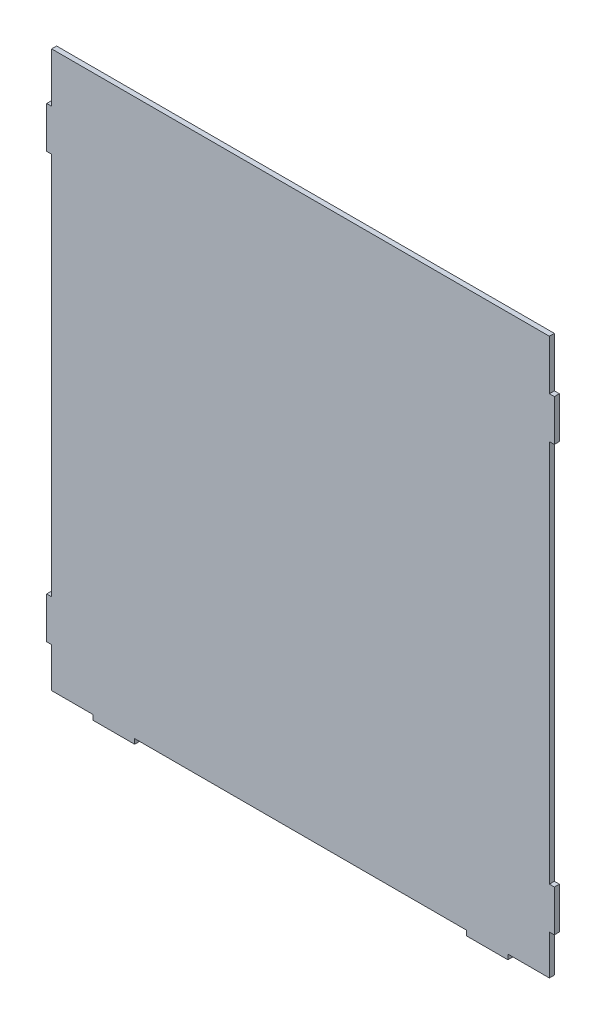
SolidWorks part; units mm, degrees
material "Maple"
ref_plane "Front Plane" through (0, 0, 0) normal (0, 0, 1) x (1, 0, 0)
ref_plane "Top Plane" through (0, 0, 0) normal (0, 1, 0) x (1, 0, 0)
ref_plane "Right Plane" through (0, 0, 0) normal (1, 0, 0) x (0, 0, -1)
sketch "Sketch1" plane through (0, 0, 0) normal (0, 0, 1) x (1, 0, 0)
  line L0 (6.0247, 322.5684) -> (6.0247, 175) construction
  line L1 (-293.9753, 322.5684) -> (306.0247, 322.5684)
  line L2 (-293.9753, 322.5684) -> (-293.9753, 262.5684)
  line L3 (-293.9753, -347.4316) -> (-243.9753, -347.4316)
  line L4 (306.0247, 322.5684) -> (306.0247, 262.5684)
  line L5 (-293.9753, -299.4316) -> (-293.9753, -347.4316)
  line L6 (-293.9753, 212.5684) -> (-293.9753, -249.4316)
  line L7 (306.0247, -299.4316) -> (306.0247, -347.4316)
  line L12 (306.0247, 212.5684) -> (306.0247, -249.4316)
  line L13 (6.0247, 322.5684) -> (6.0247, -377.5) construction
  line L14 (256.0247, -347.4316) -> (256.0247, -353.4316)
  line L21 (256.0247, -353.4316) -> (206.0247, -353.4316)
  line L22 (-193.9753, -347.4316) -> (206.0247, -347.4316)
  line L23 (312.0247, 212.5684) -> (306.0247, 212.5684)
  line L24 (6.0247, 175) -> (15.5145, 175) construction
  line L32 (-243.9753, -347.4316) -> (-243.9753, -353.4316)
  line L39 (-299.9753, 262.5684) -> (-293.9753, 262.5684)
  line L40 (-299.9753, 262.5684) -> (-299.9753, 212.5684)
  line L41 (-299.9753, 212.5684) -> (-293.9753, 212.5684)
  line L43 (-243.9753, -353.4316) -> (-193.9753, -353.4316)
  line L44 (-193.9753, -347.4316) -> (-193.9753, -353.4316)
  line L46 (312.0247, 262.5684) -> (306.0247, 262.5684)
  line L47 (312.0247, 262.5684) -> (312.0247, 212.5684)
  line L54 (-299.9753, -299.4316) -> (-293.9753, -299.4316)
  line L56 (206.0247, -347.4316) -> (206.0247, -353.4316)
  line L57 (256.0247, -347.4316) -> (306.0247, -347.4316)
  line L58 (306.0247, -249.4316) -> (312.0247, -249.4316)
  line L59 (312.0247, -249.4316) -> (312.0247, -299.4316)
  line L60 (312.0247, -299.4316) -> (306.0247, -299.4316)
  line L61 (-149.9753, 287.5684) -> (-149.9753, 322.5684) construction
  line L62 (-149.9753, 287.5684) -> (-149.9753, 237.5) construction
  line L63 (6.0247, 112.5178) -> (6.0247, 62.5) construction
  line L64 (-299.9753, -299.4316) -> (-299.9753, -249.4316)
  line L65 (-299.9753, -249.4316) -> (-293.9753, -249.4316)
  point P0 (0, 0)
  point P8 (6.0247, 175)
  dimension "D1" = 670
  dimension "D2" = 600
  dimension "D3" = 50
  dimension "D4" = 48
  dimension "D7" = 6
  dimension "D8" = 48
  dimension "D9" = 60
  dimension "D10" = 670
  dimension "D12" = 50
  dimension "D13" = 60
  dimension "D14" = 6
  dimension "D15" = 50
  dimension "D16" = 6
  dimension "D17" = 6
  dimension "D18" = 300
  dimension "D21" = 144
  dimension "D24" = 0
  dimension "D25" = 50
  dimension "D26" = 50
  dimension "D27" = 6
  dimension "D28" = 6
  dimension "D29" = 6
  dimension "D30" = 50
  dimension "D31" = 6
  dimension "D32" = 6
  dimension "D33" = 50
extrude "Boss-Extrude1" add sketch "Sketch1" along normal blind 6
